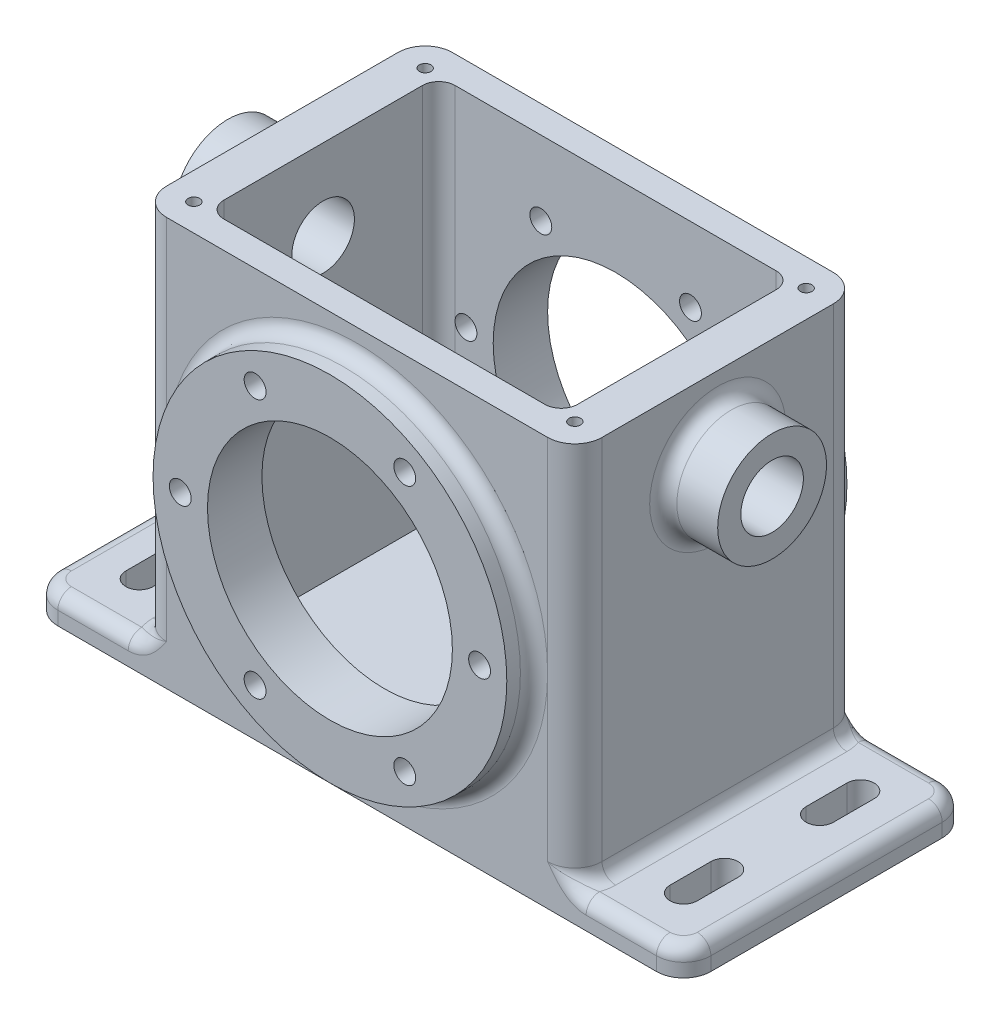
SolidWorks part; units mm, degrees
material "Cast Alloy Steel"
ref_plane "Front Plane" through (0, 0, 0) normal (0, 0, 1) x (1, 0, 0)
ref_plane "Top Plane" through (0, 0, 0) normal (0, 1, 0) x (1, 0, 0)
ref_plane "Right Plane" through (0, 0, 0) normal (1, 0, 0) x (0, 0, -1)
sketch "Sketch2" plane through (0, 0, 0) normal (0, 1, 0) x (1, 0, 0)
  line L0 (-76.2, 33.3375) -> (76.2, -33.3375) construction
  line L1 (-76.2, 33.3375) -> (76.2, 33.3375)
  line L2 (-76.2, 33.3375) -> (-76.2, -33.3375)
  line L3 (-76.2, -33.3375) -> (76.2, -33.3375)
  line L4 (76.2, 33.3375) -> (76.2, -33.3375)
  dimension "D1" = 152.4
  dimension "D2" = 66.675
extrude "Base Extrude" add sketch "Sketch2" along normal blind 6.35
sketch "Sketch4" plane through (0, 6.35, 0) normal (0, 1, 0) x (1, 0, 0)
  line L0 (76.2, 33.3375) -> (-76.2, 33.3375) construction
  line L1 (50.8, -33.3375) -> (-50.8, -33.3375)
  line L2 (50.8, -33.3375) -> (50.8, 33.3375)
  line L3 (50.8, 33.3375) -> (-50.8, 33.3375)
  line L4 (-50.8, -33.3375) -> (-50.8, 33.3375)
  line L5 (50.8, -33.3375) -> (-50.8, 33.3375) construction
  line L6 (50.8, 33.3375) -> (-50.8, -33.3375) construction
  point P0 (0, 0)
  dimension "D1" = 101.6
extrude "Secondary Extrude" add sketch "Sketch4" along normal blind 88.9
fillet "Corner Fillet" radius 6.35 8 edges at (76.2, 3.175, 33.3375) (76.2, 3.175, -33.3375) (-76.2, 3.175, 33.3375) (-76.2, 3.175, -33.3375) (-50.8, 50.8, -33.3375) (-50.8, 50.8, 33.3375) (50.8, 50.8, -33.3375) (50.8, 50.8, 33.3375)
fillet "Face Fillet" radius 3.175 16 edges at (48.9401, 6.35, 31.4776) (50.8, 6.35, 0) (48.9401, 6.35, -31.4776) (57.15, 6.35, -33.3375) (74.3401, 6.35, -31.4776) (76.2, 6.35, 0) (74.3401, 6.35, 31.4776) (57.15, 6.35, 33.3375) (-74.3401, 6.35, -31.4776) (-57.15, 6.35, -33.3375) (-48.9401, 6.35, -31.4776) (-50.8, 6.35, 0) (-48.9401, 6.35, 31.4776) (-57.15, 6.35, 33.3375) (-74.3401, 6.35, 31.4776) (-76.2, 6.35, 0)
sketch "Sketch5" plane through (0, 95.25, 0) normal (0, 1, 0) x (1, 0, 0)
  line L0 (44.45, 33.3375) -> (-44.45, 33.3375) construction
  line L1 (-37.465, 26.9875) -> (37.465, 26.9875)
  line L2 (-41.275, 23.1775) -> (-41.275, -23.1775)
  line L3 (-37.465, -26.9875) -> (37.465, -26.9875)
  line L4 (41.275, 23.1775) -> (41.275, -23.1775)
  line L5 (50.8, -26.9875) -> (50.8, 26.9875) construction
  line L6 (-44.45, -33.3375) -> (44.45, -33.3375) construction
  line L7 (-50.8, 26.9875) -> (-50.8, -26.9875) construction
  arc A0 (-41.275, -23.1775) -> (-37.465, -26.9875) centre (-37.465, -23.1775) ccw
  arc A1 (37.465, -26.9875) -> (41.275, -23.1775) centre (37.465, -23.1775) ccw
  arc A2 (37.465, 26.9875) -> (41.275, 23.1775) centre (37.465, 23.1775) cw
  arc A3 (-37.465, 26.9875) -> (-41.275, 23.1775) centre (-37.465, 23.1775) ccw
  dimension "D5" = 3.81
  dimension "D1" = 6.35
  dimension "D2" = 9.525
  dimension "D3" = 6.35
  dimension "D4" = 9.525
extrude "Top Cut" cut sketch "Sketch5" against normal blind 88.9
sketch "Sketch6" plane through (0, 0, 33.3375) normal (0, 0, 1) x (1, 0, 0)
  line L0 (-44.45, 95.25) -> (44.45, 95.25) construction
  circle A0 centre (0, 47.625) radius 41.275
  point P5 (0, 0)
  point P6 (0, 0)
  dimension "D1" = 47.625
  dimension "D2" = 82.55
extrude "Front Boss" add sketch "Sketch6" along normal blind 6.35
mirror "Mirror1" about plane through (0, 0, 0) normal (0, 0, 1) of "Front Boss"
sketch "Sketch7" plane through (50.8, 0, 0) normal (1, 0, 0) x (0, 0, -1)
  line L0 (-26.9875, 95.25) -> (26.9875, 95.25) construction
  circle A0 centre (0, 76.2) radius 12.7
  point P5 (0, 0)
  dimension "D1" = 25.4
  dimension "D2" = 19.05
extrude "Side Boss" add sketch "Sketch7" along normal blind 12.7
mirror "Mirror2" about plane through (0, 0, 0) normal (1, 0, 0) of "Side Boss"
sketch "Sketch8" plane through (0, 0, 39.6875) normal (0, 0, 1) x (1, 0, 0)
  circle A0 centre (0, 47.625) radius 28.575
  circle A1 centre (0, 47.625) radius 41.275 construction
  dimension "D1" = 57.15
extrude "Center Extrude" cut sketch "Sketch8" against normal through all
sketch "Sketch9" plane through (63.5, 0, 0) normal (1, 0, 0) x (0, 0, -1)
  circle A0 centre (0, 76.2) radius 7.3025
  circle A1 centre (0, 76.2) radius 12.7 construction
  point P4 (0, 0)
  dimension "D1" = 14.605
extrude "Side Extrude" cut sketch "Sketch9" against normal through all contours A0
hole_wizard "1/4-20 Tapped Hole1" positions "Sketch13" profile "Sketch11" tap size "1/4-20" standard "ANSI Inch" end condition through all
sketch "Sketch13" plane through (0, 0, 39.6875) normal (0, 0, 1) x (1, 0, 0)
  line L0 (-41.275, 47.625) -> (-28.575, 47.625) construction
  circle A0 centre (0, 47.625) radius 41.275 construction
  circle A1 centre (0, 47.625) radius 41.275 construction
  circle A2 centre (0, 47.625) radius 28.575 construction
  point P12 (-34.925, 47.625)
cosmetic thread "Hole Thread1" parameters "D2"=6.35
sketch "Sketch11" plane through (-34.925, 47.625, 39.6875) normal (1, 0, 0) x (0, -1, 0)
  line L0 (0, 0) -> (0, 79.375)
  line L1 (0, 79.375) -> (2.5527, 79.375)
  line L2 (2.5527, 79.375) -> (2.5527, 0)
  line L5 (2.5527, 0) -> (0, 0)
  line L11 (0, -6.35) -> (0, 107.95) construction
  dimension "Thru Tap Drill Dia." = 5.1054
  dimension "Thru Tap Drill Depth" = 79.375
pattern_circular "CirPattern1" count 6 over 360 about axis through (0, 47.625, -39.6875) along (0, 0, 1) of "1/4-20 Tapped Hole1" reverse direction yes
mirror "Mirror3" about plane through (0, 0, 0) normal (0, 0, 1) of "CirPattern1"
hole_wizard "#6-32 Tapped Hole1" positions "Sketch18" profile "Sketch19" tap size "#6-32" standard "ANSI Inch"
sketch "Sketch18" plane through (0, 95.25, 0) normal (0, 1, 0) x (1, 0, 0)
  point P0 (-44.45, 26.9875)
  point P3 (44.45, 26.9875)
  point P6 (44.45, -26.9875)
  point P9 (-44.45, -26.9875)
sketch "Sketch19" plane through (-44.45, 95.25, -26.9875) normal (1, 0, 0) x (0, 0, 1)
  line L0 (0, 0) -> (0, 11.7855)
  line L1 (0, 11.7855) -> (1.3525, 10.9728)
  line L2 (1.3525, 10.9728) -> (1.3525, 0)
  line L5 (1.3525, 0) -> (0, 0)
  line L10 (0, 11.7855) -> (-1.3525, 10.9728) construction
  line L11 (0, -6.35) -> (0, 107.95) construction
  dimension "Tap Drill Dia." = 2.7051
  dimension "Tap Drill Depth" = 10.9728
  dimension "Drill Angle" = 118
cosmetic thread "Hole Thread6" parameters "D1"=9.7028, "D2"=3.5052
cosmetic thread "Hole Thread7" parameters "D1"=9.7028, "D2"=3.5052
cosmetic thread "Hole Thread8" parameters "D1"=9.7028, "D2"=3.5052
cosmetic thread "Hole Thread9" parameters "D1"=9.7028, "D2"=3.5052
sketch "Sketch20" plane through (0, 6.35, 0) normal (0, 1, 0) x (1, 0, 0)
  line L0 (-63.5, -20.6375) -> (-63.5, -11.1125) construction
  line L1 (-66.675, -20.6375) -> (-66.675, -11.1125)
  line L2 (-60.325, -20.6375) -> (-60.325, -11.1125)
  line L3 (-53.4303, -33.3375) -> (-69.85, -33.3375) construction
  line L4 (-76.2, -26.9875) -> (-76.2, 26.9875) construction
  arc A0 (-66.675, -20.6375) -> (-60.325, -20.6375) centre (-63.5, -20.6375) ccw
  arc A1 (-60.325, -11.1125) -> (-66.675, -11.1125) centre (-63.5, -11.1125) ccw
  point P2 (-63.5, -15.875)
  dimension "D3" = 12.7
  dimension "D1" = 6.35
  dimension "D2" = 9.525
  dimension "D4" = 12.7
extrude "Slot" cut sketch "Sketch20" against normal through all
pattern_linear "LPattern1" count 2 spacing 31.75 along (0, 0, -1) of "Slot"
mirror "Mirror4" about plane through (0, 0, 0) normal (1, 0, 0) of "LPattern1"
fillet "Fillet3" radius 3.175 4 edges at (41.275, 47.625, -33.3375) (-50.8, 76.2, -12.7) (50.8, 76.2, 12.7) (-41.275, 47.625, 33.3375)
